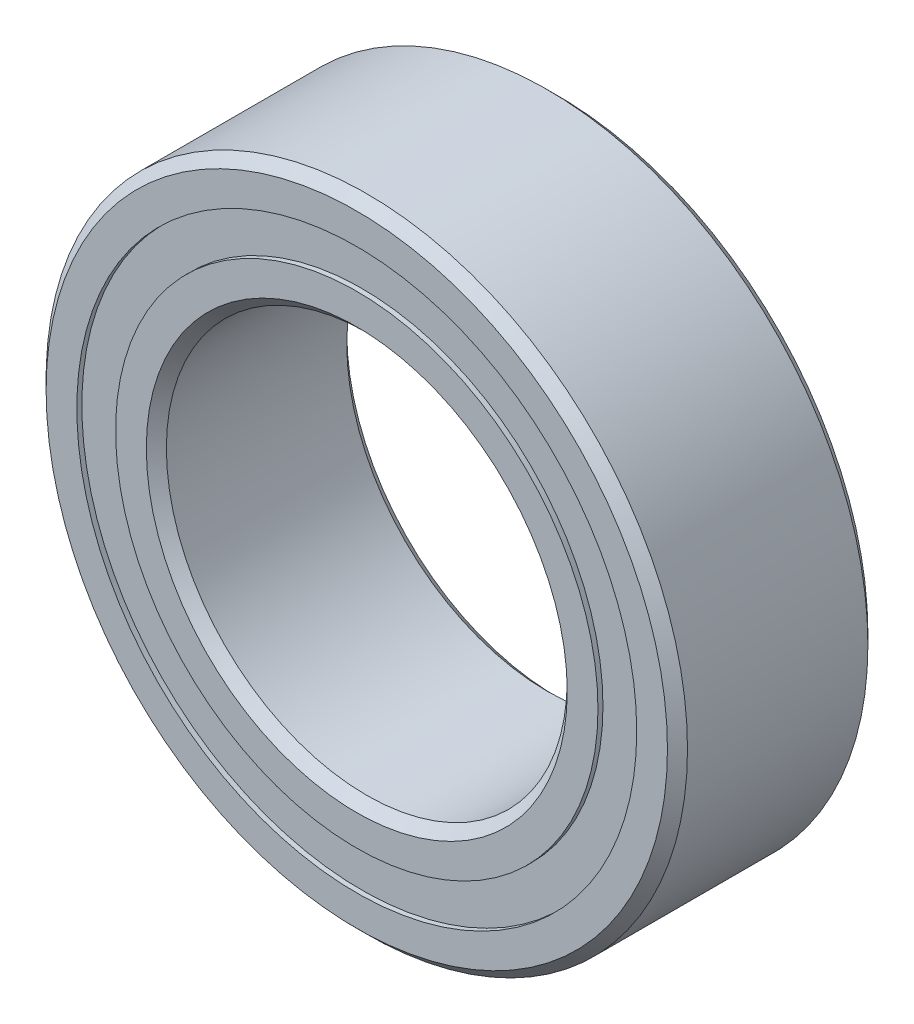
SolidWorks part; units mm, degrees
material "Plain Carbon Steel"
ref_plane "Front Plane" through (0, 0, 0) normal (0, 0, 1) x (1, 0, 0)
ref_plane "Top Plane" through (0, 0, 0) normal (0, 1, 0) x (1, 0, 0)
ref_plane "Right Plane" through (0, 0, 0) normal (1, 0, 0) x (0, 0, -1)
sketch "Sketch1" plane through (0, 0, 0) normal (1, 0, 0) x (0, 0, -1)
  line L0 (-1.25, 0) -> (1.25, 0) construction
  line L1 (0, 4) -> (0, -4) construction
  line L2 (1.125, 4) -> (-1.125, 4)
  line L3 (-1.125, 4) -> (-1.25, 3.875)
  line L4 (-1.25, 3.875) -> (-1.25, 3.4918)
  line L5 (-1.25, 3.4918) -> (-0.5556, 3.4918)
  line L6 (1.25, 3.4918) -> (0.5556, 3.4918)
  line L7 (1.25, 3.875) -> (1.25, 3.4918)
  line L8 (1.125, 4) -> (1.25, 3.875)
  line L9 (0, 4) -> (0, 3.25) construction
  line L10 (0, 3.25) -> (0, 2.5) construction
  arc A0 (-0.5556, 3.4918) -> (0.5556, 3.4918) centre (0, 3.25) cw
  point P14 (0, 2.5)
  dimension "Width" = 2.5
  dimension "OD" = 8
  dimension "D1" = 45
  dimension "D2" = 0.125
  dimension "Shaft Dia" = 5
  dimension "D3" = 1.1111
  dimension "D4" = 0.2418
revolve "Revolve1" add sketch "Sketch1" angle 360 about L0
sketch "Sketch3" plane through (0, 0, 0) normal (1, 0, 0) x (0, 0, -1)
  line L0 (-1.25, 3.0082) -> (-0.5556, 3.0082)
  line L1 (0, 4) -> (0, -4) construction
  line L2 (-1.25, 3.875) -> (-1.25, 3.4918) construction
  line L3 (-1.25, 3.0082) -> (-1.25, 2.625)
  line L4 (-1.125, 4) -> (-1.25, 3.875) construction
  line L5 (-1.25, 2.625) -> (-1.125, 2.5)
  line L6 (-1.125, 2.5) -> (1.125, 2.5)
  line L7 (1.125, 4) -> (1.125, -4) construction
  line L8 (1.125, 2.5) -> (1.25, 2.625)
  line L9 (1.25, -3.875) -> (1.25, 3.875) construction
  line L10 (1.25, 2.625) -> (1.25, 3.0082)
  line L11 (1.25, 3.0082) -> (0.5556, 3.0082)
  line L13 (1.125, 4) -> (1.25, 3.875) construction
  arc A0 (0.5556, 3.4918) -> (-0.5556, 3.4918) centre (0, 3.25) ccw construction
  arc A1 (0.5556, 3.0082) -> (-0.5556, 3.0082) centre (0, 3.25) cw
revolve "Revolve3" add sketch "Sketch3" angle 360 about L0
sketch "Sketch4" plane through (0, 0, 0) normal (1, 0, 0) x (0, 0, -1)
  line L0 (-0.6059, 3.25) -> (0.6059, 3.25)
  arc A2 (-0.6059, 3.25) -> (0.6059, 3.25) centre (0, 3.25) cw
  arc A3 (0.5556, 3.4918) -> (-0.5556, 3.4918) centre (0, 3.25) ccw construction
revolve "Revolve4" add sketch "Sketch4" angle 360 about L0
ref_axis "Axis1" through (0, 0, -1.25) along (0, 0, 1)
pattern_circular "CirPattern1" count 12 every 30 about axis through (0, 0, -1.25) along (0, 0, 1) of bodies 104
sketch "Sketch5" plane through (0, 0, 0) normal (1, 0, 0) x (0, 0, -1)
  line L0 (-1.25, 3.4918) -> (-0.5556, 3.4918) construction
  line L1 (-1.1875, 3.4918) -> (-0.6059, 3.4918)
  line L2 (-1.1875, 3.4918) -> (-1.1875, 3.0082)
  line L3 (-1.1875, 3.0082) -> (-0.6059, 3.0082)
  line L4 (-0.6059, 3.4918) -> (-0.6059, 3.0082)
  line L5 (-1.25, 3.0082) -> (-0.5556, 3.0082) construction
  line L6 (1.25, 3.4918) -> (0.5556, 3.4918) construction
  line L7 (1.1875, 3.4918) -> (0.6059, 3.4918)
  line L8 (1.1875, 3.4918) -> (1.1875, 3.0082)
  line L9 (1.1875, 3.0082) -> (0.6059, 3.0082)
  line L10 (0.6059, 3.4918) -> (0.6059, 3.0082)
  line L11 (1.25, 3.0082) -> (0.5556, 3.0082) construction
  line L12 (-1.125, 4) -> (-1.25, 3.875) construction
  point P18 (-1.1875, 3.9375)
revolve "Revolve5" add sketch "Sketch5" angle 360 about L0
sketch "Sketch6" plane through (0, 0, 0) normal (1, 0, 0) x (0, 0, -1)
  line L0 (1.25, 0) -> (-1.25, 0) construction
  line L1 (1.25, 3.4918) -> (0.4626, 3.4918)
  line L2 (1.25, 3.4918) -> (1.25, 6.9469)
  line L3 (1.25, 6.9469) -> (0.4626, 6.9469)
  line L4 (0.4626, 3.4918) -> (0.4626, 6.9469)
  dimension "Th" = 0.7874
  dimension "Flange OD" = 13.8938
revolve "Revolve6" [suppressed] add sketch "Sketch6" angle 360 about L0
equation "\"D2@Sketch1\" = \"Width@Sketch1\"*.05"
equation "\"D3@Sketch1\" = \"Width@Sketch1\"/2.25"
equation "\"D4@Sketch1\" = (((\"OD@Sketch1\"-\"Width@Sketch1\")/2)/3.25)/3.5"
equation "\"D2@CirPattern1\" = 360/\"Balls@CirPattern1\""
